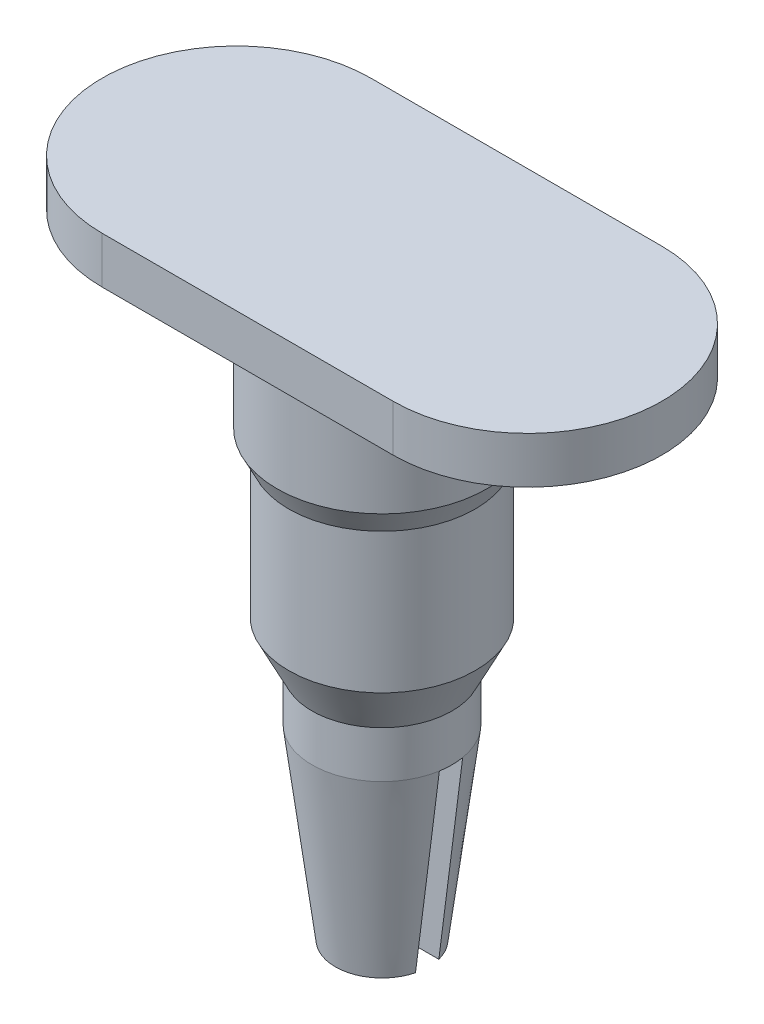
SolidWorks part; units mm, degrees
ref_plane "Alzado" through (0, 0, 0) normal (0, 0, 1) x (1, 0, 0)
ref_plane "Planta" through (0, 0, 0) normal (0, 1, 0) x (1, 0, 0)
ref_plane "Vista lateral" through (0, 0, 0) normal (1, 0, 0) x (0, 0, -1)
sketch "Sketch1" plane through (0, 0, 0) normal (0, 1, 0) x (1, 0, 0)
  line L0 (0, -10.5799) -> (0, 518.4137) construction
  line L1 (0.312, -10.608) -> (0.312, 518.3855) construction
  line L2 (-0.312, -10.6056) -> (-0.312, 518.3879) construction
  line L3 (-10.5799, 0) -> (518.4137, 0) construction
  line L4 (-0.312, 0.288) -> (0.312, 0.288)
  line L5 (0.312, -0.288) -> (-0.312, -0.288)
  arc A0 (0.312, -0.288) -> (0.312, 0.288) centre (0.312, 0) ccw
  arc A1 (-0.312, 0.288) -> (-0.312, -0.288) centre (-0.312, 0) ccw
  dimension "D3" = 0.288
  dimension "D1" = 0.312
  dimension "D2" = 0.312
extrude "Boss-Extrude1" add sketch "Sketch1" along normal blind 0.1
sketch "Sketch2" plane through (0, 0, 0) normal (0, 1, 0) x (1, 0, 0)
  circle A0 centre (0, 0) radius 0.225
  dimension "D1" = 0.45
extrude "Boss-Extrude2" add sketch "Sketch2" against normal blind 0.3
sketch "Sketch3" plane through (0, -0.3, 0) normal (0, -1, 0) x (1, 0, 0)
  circle A0 centre (0, 0) radius 0.2
  dimension "D1" = 0.4
extrude "Boss-Extrude3" add sketch "Sketch3" along normal blind 0.4
sketch "Sketch4" plane through (0, -0.7, 0) normal (0, -1, 0) x (1, 0, 0)
  circle A0 centre (0, 0) radius 0.15
  dimension "D1" = 0.3
extrude "Boss-Extrude4" add sketch "Sketch4" along normal blind 0.1
sketch "Sketch5" plane through (0, -0.8, 0) normal (0, -1, 0) x (1, 0, 0)
  circle A0 centre (0, 0) radius 0.15
  dimension "D1" = 0.3
extrude "Boss-Extrude5" add sketch "Sketch5" along normal blind 0.4
chamfer "Chamfer1" distance 0.025 distance2 0.05 1 edges at (0, -0.3, 0.225) first distance on face at (0, -0.3, 0.225)
chamfer "Chamfer2" distance 0.1 distance2 0.05 1 edges at (0, -0.7, -0.2) first distance on face at (0, -0.7, -0.2)
chamfer "Chamfer3" distance 0.4 distance2 0.05 1 edges at (0, -1.2, -0.15) first distance on face at (0, -0.7, -0.15)
sketch "Sketch6" plane through (0, 0, 0) normal (1, 0, 0) x (0, 0, -1)
  line L0 (0, -1000) -> (0, 49000) construction
  line L1 (0.025, -1000) -> (0.025, 49000) construction
  line L3 (-0.025, -1000) -> (-0.025, 49000) construction
  line L5 (0.15, -0.8) -> (-0.15, -0.8) construction
  line L6 (0.15, -0.8) -> (-0.15, -0.8) construction
  line L8 (-0.025, -0.8) -> (0.025, -0.8)
  line L9 (-0.025, -0.8) -> (-0.025, -1.3174)
  line L10 (-0.025, -1.3174) -> (0.025, -1.3174)
  line L11 (0.025, -0.8) -> (0.025, -1.3174)
  dimension "D1" = 0.025
  dimension "D2" = 0.025
extrude "Cut-Extrude1" cut sketch "Sketch6" against normal through all both and the other way through all
ref_axis "Axis1" through (0, 0.2118, 0) along (0, -1, 0)
